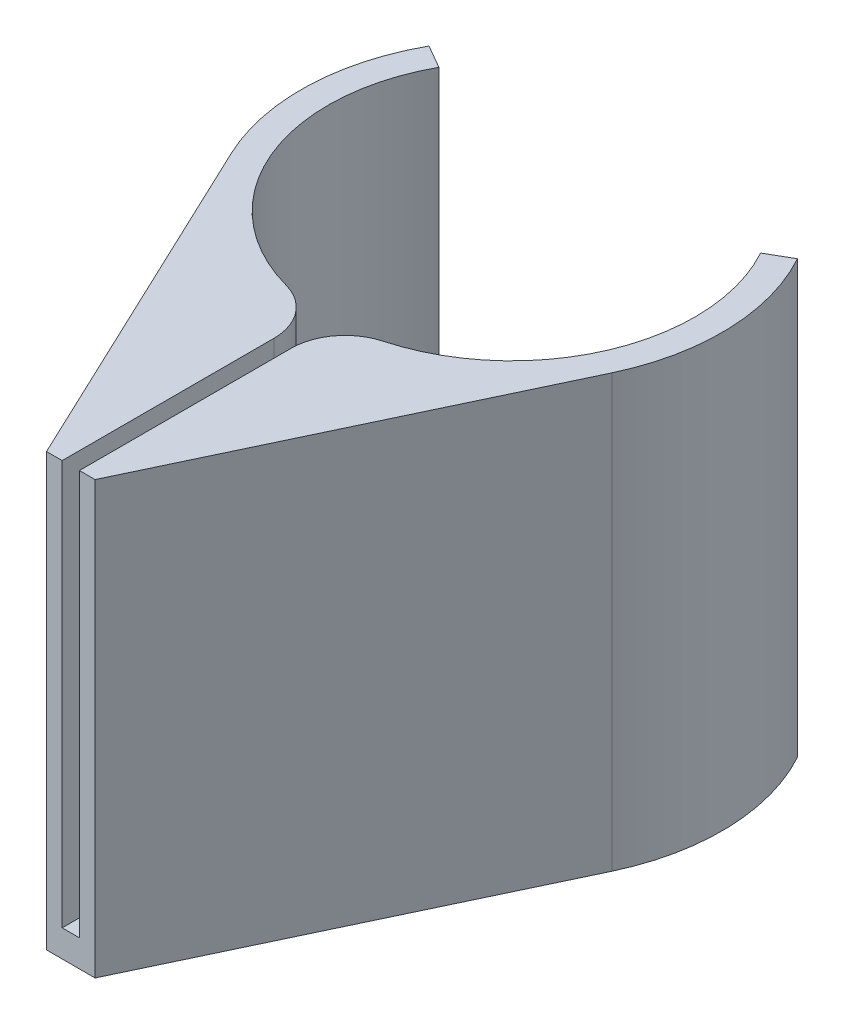
SolidWorks part; units mm, degrees
ref_plane "Front Plane" through (0, 0, 0) normal (0, 0, 1) x (1, 0, 0)
ref_plane "Top Plane" through (0, 0, 0) normal (0, 1, 0) x (1, 0, 0)
ref_plane "Right Plane" through (0, 0, 0) normal (1, 0, 0) x (0, 0, -1)
sketch "body tube profile" plane through (0, 0, 0) normal (0, 1, 0) x (1, 0, 0)
  circle A0 centre (0, 0) radius 34
  dimension "D1" = 68
sketch "Sketch2" plane through (0, 0, 0) normal (0, 1, 0) x (1, 0, 0)
  line L1 (0, 0) -> (0, -34) construction
  line L2 (-35.2539, -16.6782) -> (-4.5, -81.685)
  line L13 (29.4449, 17) -> (33.775, 19.5) construction
  line L14 (-4.5, -81.685) -> (4.5, -81.685)
  line L15 (29.8127, 16.3463) -> (34.1437, 18.8469)
  line L16 (0, -37.4) -> (0, 37.4) construction
  line L17 (-29.8127, 16.3463) -> (-34.1437, 18.8469)
  line L18 (4.5, -81.685) -> (35.2539, -16.6782)
  circle A0 centre (0, 0) radius 39 construction
  circle A3 centre (0, 0) radius 34 construction
  arc A4 (-29.8127, 16.3463) -> (29.8127, 16.3463) centre (0, 0) ccw
  arc A6 (-34.1437, 18.8469) -> (-35.2539, -16.6782) centre (0, 0) ccw
  circle A7 centre (0, 0) radius 34 construction
  arc A8 (35.2539, -16.6782) -> (34.1437, 18.8469) centre (0, 0) ccw
  point P10 (0, -81.685)
  dimension "D2" = 9
  dimension "D3" = 120
  dimension "D4" = 81.685
  dimension "D5" = 1.5
  dimension "D6" = 5
  dimension "D1" = 5
extrude "Fin slot extrude" add sketch "Sketch2" along normal blind 80 contours L17 region at (0, 0, 39.7439)
sketch "Sketch3" plane through (0, 80, 0) normal (0, 1, 0) x (1, 0, 0)
  line L0 (0, -81.685) -> (0, -34) construction
  line L1 (-4.5, -81.685) -> (4.5, -81.685) construction
  line L2 (1.6, -81.685) -> (1.6, -33.9623)
  line L3 (-1.6, -81.685) -> (-1.6, -33.9623)
  line L4 (-1.6, -81.685) -> (1.6, -81.685)
  arc A0 (-29.8127, 16.3463) -> (29.8127, 16.3463) centre (0, 0) ccw construction
  arc A1 (-1.6, -33.9623) -> (1.6, -33.9623) centre (0, 0) ccw
  dimension "D1" = 1.6
extrude "Fin slot" cut sketch "Sketch3" against normal offset from surface (75 mm away) 5 up to face at (0, 0, 22.0523)
fillet "Fillet1" radius 10 3 edges at (0, 5, 34) (1.6, 42.5, 33.9623) (-1.6, 42.5, 33.9623)
